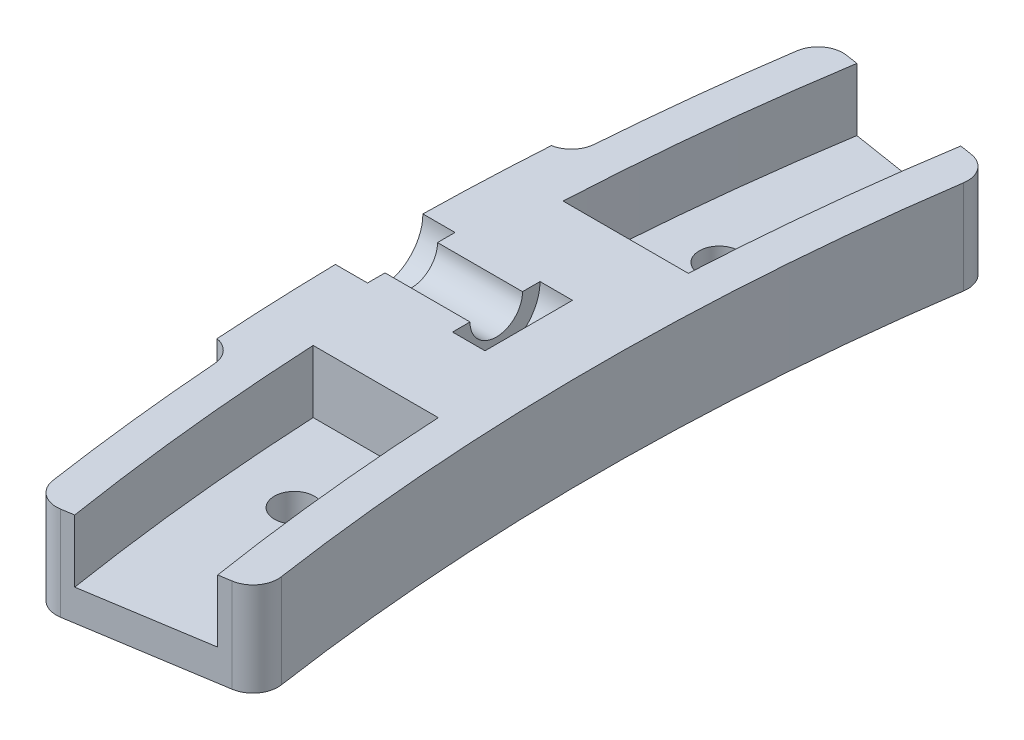
SolidWorks part; units mm, degrees
ref_plane "Front Plane" through (0, 0, 0) normal (0, 0, 1) x (1, 0, 0)
ref_plane "Top Plane" through (0, 0, 0) normal (0, 1, 0) x (1, 0, 0)
ref_plane "Right Plane" through (0, 0, 0) normal (1, 0, 0) x (0, 0, -1)
sketch "Sketch1" plane through (0, 0, 0) normal (0, 1, 0) x (1, 0, 0)
  line L0 (0, 0) -> (-197.5377, -31.2869) construction
  line L1 (0, 0) -> (-197.5377, 31.2869) construction
  line L2 (0, 0) -> (-195, 0) construction
  line L3 (-197.5377, 31.2869) -> (-187.6608, 29.7225)
  line L4 (-187.6608, -29.7225) -> (-197.5377, -31.2869)
  line L5 (0, 0) -> (-200.5007, -31.7562) construction
  line L6 (0, 0) -> (-200.5007, 31.7562) construction
  line L7 (-200.5007, 31.7562) -> (-184.6977, 29.2532)
  line L8 (-200.5007, -31.7562) -> (-184.6977, -29.2532)
  arc A0 (-197.5377, 31.2869) -> (-197.5377, -31.2869) centre (0, 0) ccw
  arc A1 (-187.6608, 29.7225) -> (-187.6608, -29.7225) centre (0, 0) ccw
  arc A2 (-192.5992, -30.5047) -> (-192.5992, 30.5047) centre (0, 0) cw construction
  arc A4 (-184.6977, 29.2532) -> (-184.6977, -29.2532) centre (0, 0) ccw
  arc A5 (-200.5007, 31.7562) -> (-200.5007, -31.7562) centre (0, 0) ccw
  dimension "D1" = 200
  dimension "D2" = 190
  dimension "D3" = 5
  dimension "D5" = 187
  dimension "D6" = 203
  dimension "D4" = 18
extrude "Boss-Extrude1" add sketch "Sketch1" along normal blind 7.5 contours A1 L3 A0 L4 | L7 A5 L8 A0 | A4 L7 A1 L8 region at (-200.6761, 0, 0) region at (-194.2416, 0, 0) region at (-187.7297, 0, 0)
ref_plane "Plane1" through (-195, 0, 0) normal (1, 0, 0) x (0, 0, -1)
sketch "Sketch19" plane through (0, 0, 0) normal (0, 1, 0) x (1, 0, 0)
  line L0 (0, 0) -> (-204.0621, 13.3749) construction
  line L1 (0, 0) -> (-204.0621, -13.3749) construction
  line L4 (0, 0) -> (-204.5, 0) construction
  line L5 (-204.0621, 13.3749) -> (-202.5654, 13.2768)
  line L6 (-204.0621, -13.3749) -> (-202.5654, -13.2768)
  arc A0 (-204.0621, 13.3749) -> (-204.0621, -13.3749) centre (0, 0) ccw
  arc A1 (-200.5007, 31.7562) -> (-200.5007, -31.7562) centre (0, 0) ccw construction
  arc A2 (-202.5654, 13.2768) -> (-202.5654, -13.2768) centre (0, 0) ccw
  dimension "D1" = 204.5
  dimension "D2" = 3.75
extrude "Boss-Extrude2" add sketch "Sketch19" along normal blind 7.5
sketch "Sketch15" plane through (0, 7.5, 0) normal (0, 1, 0) x (1, 0, 0)
  line L0 (-187.6608, -29.7225) -> (-197.5377, -31.2869) construction
  line L1 (-185, 10) -> (-205, 10)
  line L2 (-185, 10) -> (-185, -10)
  line L3 (-185, -10) -> (-205, -10)
  line L4 (-205, 10) -> (-205, -10)
  line L5 (-185, 10) -> (-205, -10) construction
  line L6 (-185, -10) -> (-205, 10) construction
  line L7 (-197.5377, 31.2869) -> (-187.6608, 29.7225) construction
  line L8 (-187.6608, -29.7225) -> (-197.5377, -31.2869)
  line L9 (-197.5377, 31.2869) -> (-187.6608, 29.7225)
  arc A2 (-187.6608, 29.7225) -> (-187.6608, -29.7225) centre (0, 0) ccw construction
  arc A3 (-197.5377, 31.2869) -> (-197.5377, -31.2869) centre (0, 0) ccw construction
  arc A4 (-187.6608, 29.7225) -> (-187.6608, -29.7225) centre (0, 0) ccw
  arc A5 (-197.5377, 31.2869) -> (-197.5377, -31.2869) centre (0, 0) ccw
  point P0 (-195, 0)
  line M5 (-200.5007, -31.7562) -> (-184.6977, -29.2532)
  line M7 (-184.6977, 29.2532) -> (-200.5007, 31.7562)
  dimension "D1" = 20
  dimension "D2" = 20
extrude "Cut-Extrude1" cut sketch "Sketch15" against normal blind 5 contours A5 L1 A4 M7 | L3 A5 A4 M5 region at (-193.9153, 7.5, -20.2762) region at (-193.9153, 7.5, 20.2762)
ref_plane "Plane2" through (-195, 0, 0) normal (-1, 0, 0) x (0, 0, 1)
sketch "Sketch12" plane through (0, 0, 0) normal (0, 1, 0) x (1, 0, 0)
  line L0 (0, 0) -> (-194.258, -16.9954) construction
  line L1 (0, 0) -> (-193.3317, -25.4526) construction
  line L2 (0, 0) -> (-195, 0) construction
  line L3 (0, 0) -> (-195, 0) construction
  line L4 (0, 0) -> (-194.258, 16.9954) construction
  line L5 (0, 0) -> (-193.3317, 25.4526) construction
  arc A0 (-192.5992, 30.5047) -> (-192.5992, -30.5047) centre (0, 0) ccw construction
  dimension "D1" = 10
  dimension "D2" = 15
hole_wizard "Ø3.2 (3.2) Diameter Hole1" positions "Sketch18" profile "Sketch17" hole size "Ø3.2" standard "ISO" end condition through all
sketch "Sketch18" plane through (0, 0, 0) normal (0, -1, 0) x (-1, 0, 0)
  point P3 (194.258, -16.9954)
  point P6 (194.258, 16.9954)
sketch "Sketch17" plane through (-194.258, 0, 16.9954) normal (1, 0, 0) x (0, 0, -1)
  line L0 (0, 0) -> (0, 7.5)
  line L1 (0, 7.5) -> (1.6, 7.5)
  line L2 (1.6, 7.5) -> (1.6, 0)
  line L5 (1.6, 0) -> (0, 0)
  line L11 (0, -6.35) -> (0, 107.95) construction
  dimension "Thru Hole Dia." = 3.2
  dimension "Thru Hole Depth" = 7.5
sketch "Sketch20" plane through (0, 0, 0) normal (0, 1, 0) x (1, 0, 0)
  line L0 (-205, 0) -> (-192.5, 0) construction
  line L1 (0, 0) -> (-205, 0) construction
  arc A2 (-204.0621, 13.3749) -> (-204.0621, -13.3749) centre (0, 0) ccw construction
  point P3 (-204.5, 0)
  dimension "D1" = 205
  dimension "D2" = 12.5
ref_plane "Plane3" through (-192.5, 0, 0) normal (1, 0, 0) x (0, 0, -1)
sketch "Sketch21" plane through (-192.5, 0, 0) normal (1, 0, 0) x (0, 0, -1)
  line L0 (29.2532, 7.5) -> (-29.2532, 7.5) construction
  circle A0 centre (0, 7.5) radius 3.5
  dimension "D1" = 7
extrude "Cut-Extrude2" cut sketch "Sketch21" against normal blind 2.6
sketch "Sketch22" plane through (-195.1, 0, 0) normal (1, 0, 0) x (0, 0, -1)
  line L0 (29.2532, 7.5) -> (-29.2532, 7.5) construction
  circle A0 centre (0, 7.5) radius 2.1
  dimension "D1" = 4.2
ref_plane "Plane4" through (-204.5, 0, 0) normal (1, 0, 0) x (0, 0, -1)
sketch "Sketch23" plane through (-204.5, 0, 0) normal (1, 0, 0) x (0, 0, -1)
  circle A0 centre (0, 7.5) radius 3.5
  dimension "D1" = 7
extrude "Cut-Extrude3" cut sketch "Sketch23" along normal blind 2.6
extrude "Cut-Extrude4" cut sketch "Sketch22" against normal through all contours A0
fillet "Fillet1" radius 2 4 edges at (-200.5007, 3.75, -31.7562) (-184.6977, 3.75, -29.2532) (-184.6977, 3.75, 29.2532) (-200.5007, 3.75, 31.7562)
fillet "Fillet2" radius 2 2 edges at (-202.5654, 3.75, -13.2768) (-202.5654, 3.75, 13.2768)
